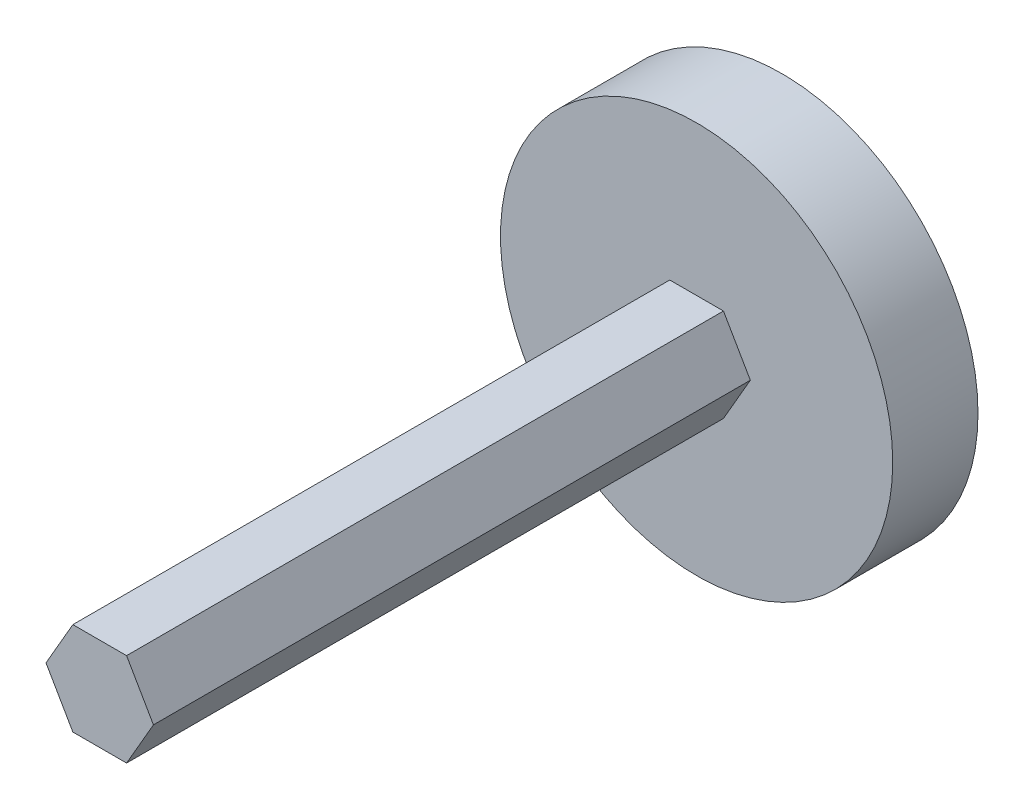
SolidWorks part; units mm, degrees
ref_plane "Front Plane" through (0, 0, 0) normal (0, 0, 1) x (1, 0, 0)
ref_plane "Top Plane" through (0, 0, 0) normal (0, 1, 0) x (1, 0, 0)
ref_plane "Right Plane" through (0, 0, 0) normal (1, 0, 0) x (0, 0, -1)
sketch "Sketch2" plane through (0, 0, 0) normal (0, 0, 1) x (1, 0, 0)
  line L1 (-6.3, 0) -> (-3.15, -5.456)
  line L2 (-3.15, -5.456) -> (3.15, -5.456)
  line L3 (3.15, -5.456) -> (6.3, 0)
  line L4 (6.3, 0) -> (3.15, 5.456)
  line L5 (3.15, 5.456) -> (-3.15, 5.456)
  line L6 (-3.15, 5.456) -> (-6.3, 0)
  circle A0 centre (0, 0) radius 23
  circle A1 centre (0, 0) radius 5.456 construction
  dimension "D1" = 46
  dimension "D2" = 6.3
extrude "Boss-Extrude1" add sketch "Sketch2" along normal blind 10
extrude "Boss-Extrude2" add sketch "Sketch2<2>" along normal blind 80 contours L5 L6 L1 L2 L3 L4 region at (0, 0, 0)
sketch "Sketch2<2>" plane through (0, 0, 0) normal (0, 0, 1) x (1, 0, 0) same geometry as "Sketch2"
sketch "Sketch5" plane through (0, 0, 0) normal (0, 0, -1) x (-1, 0, 0)
  circle A0 centre (0, 0) radius 17.5
  circle A1 centre (0, 10) radius 0.5
  circle A2 centre (-7.0683, 7.0739) radius 0.5
  circle A3 centre (7.0683, 7.0739) radius 0.5
  circle A4 centre (-10, 0.0079) radius 0.5
  circle A5 centre (-7.0795, -7.0626) radius 0.5
  circle A6 centre (-0.0159, -10) radius 0.5
  circle A7 centre (7.057, -7.0851) radius 0.5
  circle A8 centre (9.9615, -0.0079) radius 0.5
  dimension "D1" = 35
  dimension "D2" = 1
  dimension "D4" = 1
  dimension "D7" = 1
  dimension "D10" = 1
  dimension "D14" = 1
  dimension "D17" = 1
  dimension "D20" = 1
  dimension "D23" = 1
  dimension "D3" = 10
  dimension "D5" = 10
  dimension "D6" = 7.65
  dimension "D8" = 10
  dimension "D9" = 7.65
  dimension "D11" = 10
  dimension "D12" = 7.65
  dimension "D13" = 10
  dimension "D15" = 10
  dimension "D16" = 7.65
  dimension "D18" = 10
  dimension "D19" = 7.65
  dimension "D21" = 10
  dimension "D22" = 7.65
  dimension "D24" = 7.65
  dimension "D25" = 7.65
  dimension "D26" = 9.9615
extrude "Boss-Extrude3" add sketch "Sketch5" along normal blind 5 contours A2 | A1 | A3 | A5 | A4 | A6 | A7 | A8 region at (0, 10, 0) region at (7.0683, 7.0739, 0) region at (-7.0683, 7.0739, 0) region at (7.0795, -7.0626, 0)
